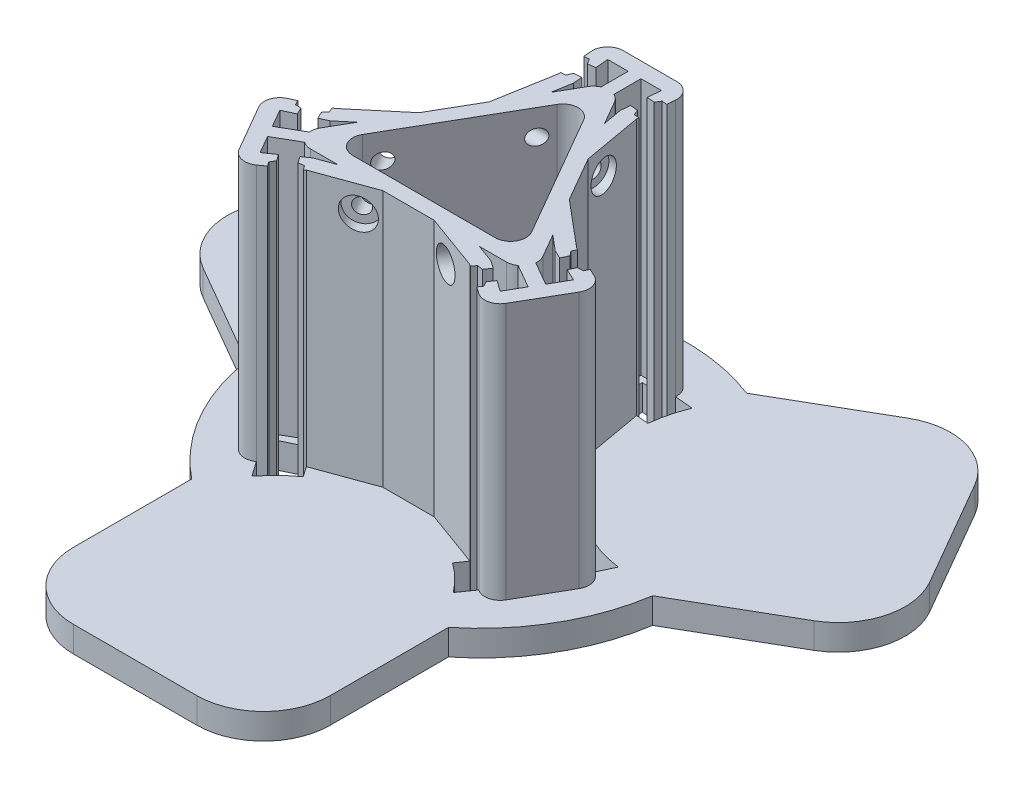
SolidWorks part; units mm, degrees
ref_plane "前视基准面" through (0, 0, 0) normal (0, 0, 1) x (1, 0, 0)
ref_plane "上视基准面" through (0, 0, 0) normal (0, 1, 0) x (1, 0, 0)
ref_plane "右视基准面" through (0, 0, 0) normal (1, 0, 0) x (0, 0, -1)
other "Configuration Table"
sketch "草图1" plane through (0, 0, 0) normal (0, 1, 0) x (1, 0, 0)
  line L0 (0, 0) -> (0, 132.3895) construction
  line L1 (0, 0) -> (0, -137.3851) construction
  line L2 (0, 0) -> (215.1509, 0) construction
  line L3 (0, 0) -> (134.3926, 77.5916) construction
  line L4 (0, 0) -> (-134.3926, 77.5916) construction
  line L5 (0, -40) -> (55.6916, -40) construction
  line L6 (-25, -31.225) -> (-25, -67.225)
  line L7 (-14.5416, 37.2631) -> (-45.7185, 55.2631)
  line L8 (25, -67.225) -> (-25, -67.225)
  line L9 (-70.7185, 11.9619) -> (-45.7185, 55.2631)
  line L10 (25, -31.225) -> (25, -67.225)
  line L11 (-39.5416, -6.0381) -> (-70.7185, 11.9619)
  line L12 (39.5416, -6.0381) -> (70.7185, 11.9619)
  line L13 (45.7185, 55.2631) -> (70.7185, 11.9619)
  line L14 (14.5416, 37.2631) -> (45.7185, 55.2631)
  circle A0 centre (0, 0) radius 40
  circle A1 centre (0, -40) radius 25 construction
  circle A2 centre (-34.641, 20) radius 25 construction
  circle A3 centre (34.641, 20) radius 25 construction
  point P16 (0, 0)
  point P23 (0, -67.225)
  point P32 (0, 0)
  dimension "D2" = 80
  dimension "D3" = 50
  dimension "D5" = 25
  dimension "D1" = 120
  dimension "D6" = 36
  dimension "D4" = 3
  dimension "D7" = 3
extrude "凸台-拉伸1" add sketch "草图1" along normal blind 5 contours A0 | A0 L7 L9 L11 | A0 L12 L13 L14 | A0 L6 L8 L10 region at (0, 0, 52.1112) region at (0, 0, 0) region at (-45.1296, 0, -26.0556) region at (45.1296, 0, -26.0556)
sketch "草图3" plane through (0, 5, 0) normal (0, 1, 0) x (1, 0, 0)
  line L0 (0, 28) -> (24.2487, -14)
  line L1 (0, 0) -> (134.3926, 77.5916) construction
  line L2 (0, 0) -> (0, 132.3895) construction
  line L3 (0, 0) -> (0, -137.3851) construction
  line L4 (0, 0) -> (-134.3926, 77.5916) construction
  line L5 (0, 0) -> (0, -137.3851) construction
  line L6 (0, 0) -> (-134.3926, 77.5916) construction
  line L7 (0, 0) -> (134.3926, 77.5916) construction
  line L8 (24.2487, -14) -> (-24.2487, -14)
  line L9 (-24.2487, -14) -> (0, 28)
  line L10 (0, 22) -> (19.0526, -11)
  line L11 (19.0526, -11) -> (-19.0526, -11)
  line L12 (-19.0526, -11) -> (0, 22)
  line L13 (5, -14) -> (15.9238, -17.9759)
  line L14 (15.9238, -17.9759) -> (24.3288, -23.8612)
  line L15 (0, 0) -> (24.2487, -14) construction
  line L17 (23.5295, -4.8024) -> (32.8288, -9.1388)
  line L18 (24.3288, -23.8612) -> (32.8288, -9.1388)
  line L19 (14.6244, 2.6699) -> (23.5295, -4.8024)
  line L20 (-5, -14) -> (-15.9238, -17.9759)
  line L21 (-15.9238, -17.9759) -> (-24.3288, -23.8612)
  line L22 (-32.8288, -9.1388) -> (-24.3288, -23.8612)
  line L23 (-23.5295, -4.8024) -> (-32.8288, -9.1388)
  line L24 (-14.6244, 2.6699) -> (-23.5295, -4.8024)
  line L25 (-9.6244, 11.3301) -> (-7.6057, 22.7784)
  line L26 (-7.6057, 22.7784) -> (-8.5, 33)
  line L27 (8.5, 33) -> (-8.5, 33)
  line L28 (7.6057, 22.7784) -> (8.5, 33)
  line L29 (9.6244, 11.3301) -> (7.6057, 22.7784)
  line L30 (-14.6244, 2.6699) -> (-23.5295, -4.8024)
  line L31 (-23.5295, -4.8024) -> (-32.8288, -9.1388)
  line L32 (-32.8288, -9.1388) -> (-24.3288, -23.8612)
  line L33 (-15.9238, -17.9759) -> (-24.3288, -23.8612)
  line L34 (-5, -14) -> (-15.9238, -17.9759)
  line L35 (5, -14) -> (15.9238, -17.9759)
  line L36 (15.9238, -17.9759) -> (24.3288, -23.8612)
  line L37 (24.3288, -23.8612) -> (32.8288, -9.1388)
  line L38 (23.5295, -4.8024) -> (32.8288, -9.1388)
  line L39 (14.6244, 2.6699) -> (23.5295, -4.8024)
  line L40 (5.529, -11) -> (17.321, -15.2919)
  line L41 (17.321, -15.2919) -> (23.3677, -19.5259)
  line L42 (23.3677, -19.5259) -> (28.5938, -10.4741)
  line L43 (21.9037, -7.3544) -> (28.5938, -10.4741)
  line L44 (12.2908, 0.7118) -> (21.9037, -7.3544)
  line L45 (-12.2908, 0.7118) -> (-21.9037, -7.3544)
  line L46 (-21.9037, -7.3544) -> (-28.5938, -10.4741)
  line L47 (-28.5938, -10.4741) -> (-23.3677, -19.5259)
  line L48 (-17.321, -15.2919) -> (-23.3677, -19.5259)
  line L49 (-5.529, -11) -> (-17.321, -15.2919)
  line L50 (6.7618, 10.2882) -> (4.5827, 22.6464)
  line L51 (4.5827, 22.6464) -> (5.2261, 30)
  line L52 (5.2261, 30) -> (-5.2261, 30)
  line L53 (-4.5827, 22.6464) -> (-5.2261, 30)
  line L54 (-6.7618, 10.2882) -> (-4.5827, 22.6464)
  line L55 (-12.696, 0.3717) -> (-21.9037, -7.3544) construction
  line L56 (-6.0261, -11.1809) -> (-17.321, -15.2919) construction
  line L57 (6.0261, -11.1809) -> (17.321, -15.2919) construction
  line L58 (12.696, 0.3717) -> (21.9037, -7.3544) construction
  line L59 (-6.6699, 10.8092) -> (-4.5827, 22.6464) construction
  line L60 (6.6699, 10.8092) -> (4.5827, 22.6464) construction
  point P13 (12.1244, 7)
  point P17 (0, 0)
  point P20 (28.5788, -16.5)
  point P38 (0, 0)
  dimension "D1" = 3
  dimension "D2" = 14
  dimension "D5" = 5
  dimension "D6" = 20
  dimension "D7" = 195
  dimension "D8" = 8.5
  dimension "D9" = 5
  dimension "D3" = 3
  dimension "D11" = 0
  dimension "D12" = 3
  dimension "D10" = 3
extrude "凸台-拉伸2" add sketch "草图3" along normal blind 50 contours L11 L49 L8 L40 | L0 L44 L43 L42 L41 L40 L8 L13 L14 L18 L17 L19 | L8 L49 L48 L47 L46 L45 L9 L24 L23 L22 L21 L20 | L12 L54 L9 L45 | L9 L54 L53 L52 L51 L50 L0 L29 L28 L27 L26 L25 | L50 L10 L44 L0 | L44 L10 L11 L40 L8 L0 | L49 L11 L12 L45 L9 L8 | L54 L12 L10 L50 L0 L9 region at (11.0102, 5, -6.3568) region at (7.6825, 5, -15.2732) region at (18.8298, 5, 1.3608) region at (5.7808, 5, -14.5686) region at (21.4232, 5, 9.5822) region at (-11.0102, 5, -6.3568) region at (0, 5, 12.7135) region at (-17.1502, 5, 0.936) region at (-15.8779, 5, 5.0251)
fillet "圆角1" radius 13 6 edges at (25, 2.5, 67.225) (-25, 2.5, 67.225) (-70.7185, 2.5, -11.9619) (-45.7185, 2.5, -55.2631) (70.7185, 2.5, -11.9619) (45.7185, 2.5, -55.2631)
fillet "圆角2" radius 3 6 edges at (0, 30, -28) (0, 30, -22) (24.2487, 30, 14) (19.0526, 30, 11) (-19.0526, 30, 11) (-24.2487, 30, 14)
sketch "草图6" plane through (0, 0, 0) normal (0, -1, 0) x (1, 0, 0)
  line L0 (0, 0) -> (0, 137.3851) construction
  line L1 (0, 0) -> (215.1509, 0) construction
  line L2 (0, 0) -> (0, -132.3895) construction
  line L3 (0, 0) -> (0, -132.3895) construction
  line L4 (0, 0) -> (215.1509, 0) construction
  circle A1 centre (0, 0) radius 3.5
  circle A2 centre (0, 7) radius 1.5
  circle A3 centre (7, 0) radius 1.5
  circle A4 centre (-7, 0) radius 1.5
  circle A5 centre (0, -7) radius 1.5
  dimension "D1" = 7
  dimension "D2" = 3
  dimension "D3" = 3
  dimension "D4" = 7
  dimension "D5" = 7
extrude "切除-拉伸1" cut sketch "草图6" against normal blind 5
fillet "圆角3" radius 3 6 edges at (-8.5, 30, -33) (8.5, 30, -33) (32.8288, 30, 9.1388) (-32.8288, 30, 9.1388) (-24.3288, 30, 23.8612) (24.3288, 30, 23.8612)
sketch "草图7" plane through (0, 0, 0) normal (1, 0, 0) x (0, 0, -1)
  line L0 (0, 0) -> (80.2302, 0) construction
  line L1 (0, 0) -> (132.3895, 0) construction
  line L2 (0, 0) -> (0, 66.7325) construction
  line L3 (15, 0) -> (15, 66.7325) construction
  line L5 (11.3301, 55) -> (22.7784, 55) construction
  circle A0 centre (15, 50) radius 1.5
  dimension "D2" = 3
  dimension "D3" = 5
  dimension "D1" = 15
extrude "切除-拉伸2" cut sketch "草图7" against normal blind 10 and the other way blind 10
ref_plane "基准面1" through (7, 0, 0) normal (1, 0, 0) x (0, 0, -1)
sketch "草图9" plane through (7, 0, 0) normal (1, 0, 0) x (0, 0, -1)
  circle A0 centre (15, 50) radius 3
  dimension "D1" = 6
extrude "切除-拉伸3" cut sketch "草图9" along normal blind 10
mirror "镜向1" about plane through (0, 0, 0) normal (1, 0, 0) of "切除-拉伸3"
ref_axis "基准轴1" through (0, 56.7, 0) along (0, -1, 0)
pattern_circular "阵列(圆周)1" count 3 over 360 about axis through (0, 56.7, 0) along (0, -1, 0) of "切除-拉伸2", "切除-拉伸3", "镜向1"
sketch "草图10" plane through (0, 5, 0) normal (0, 1, 0) x (1, 0, 0)
  line L2 (23.3677, -19.5259) -> (28.5938, -10.4741) construction
  line L3 (23.3677, -19.5259) -> (20.0911, -17.2316)
  line L4 (17.321, -15.2919) -> (23.3677, -19.5259) construction
  line L5 (23.3677, -19.5259) -> (28.5938, -10.4741)
  line L6 (0, 0) -> (25.9808, -15) construction
  line L7 (28.5938, -10.4741) -> (24.9686, -8.7836)
  line L8 (24.9686, -8.7836) -> (20.0911, -17.2316)
  line L9 (-23.3677, -19.5259) -> (-20.0911, -17.2316)
  line L10 (-20.0911, -17.2316) -> (-24.9686, -8.7836)
  line L11 (-28.5938, -10.4741) -> (-24.9686, -8.7836)
  line L12 (-28.5938, -10.4741) -> (-23.3677, -19.5259)
  line L13 (-5.2261, 30) -> (-4.8775, 26.0152)
  line L14 (-4.8775, 26.0152) -> (4.8775, 26.0152)
  line L15 (5.2261, 30) -> (4.8775, 26.0152)
  line L16 (5.2261, 30) -> (-5.2261, 30)
  line L17 (16.4545, -6.5) -> (14.1451, -2.5)
  line L18 (2.5981, 17.5) -> (16.4545, -6.5) construction
  line L19 (14.1451, -2.5) -> (9.2376, -11)
  line L20 (11.6913, -6.75) -> (15.1554, -8.75)
  line L21 (13.8564, -11) -> (16.4545, -6.5)
  line L22 (13.8564, -11) -> (9.2376, -11)
  line L23 (-16.4545, -6.5) -> (-13.8564, -11)
  line L24 (-13.8564, -11) -> (-9.2376, -11)
  line L25 (-9.2376, -11) -> (-14.1451, -2.5)
  line L26 (-11.6913, -6.75) -> (-15.1554, -8.75)
  line L27 (2.5981, 17.5) -> (-2.5981, 17.5)
  line L28 (-2.5981, 17.5) -> (-4.9075, 13.5)
  line L29 (-4.9075, 13.5) -> (4.9075, 13.5)
  line L30 (0, 13.5) -> (0, 17.5)
  line L31 (9.2376, -11) -> (13.8564, -11)
  line L32 (-16.4545, -6.5) -> (-14.1451, -2.5)
  line L33 (2.5981, 17.5) -> (4.9075, 13.5)
  arc A0 (2.5981, 17.5) -> (-2.5981, 17.5) centre (0, 16) ccw construction
  arc A1 (-16.4545, -6.5) -> (-13.8564, -11) centre (-13.8564, -8) ccw construction
  arc A2 (13.8564, -11) -> (16.4545, -6.5) centre (13.8564, -8) ccw construction
  arc A3 (2.5981, 17.5) -> (-2.5981, 17.5) centre (0, 16) ccw
  arc A4 (-16.4545, -6.5) -> (-13.8564, -11) centre (-13.8564, -8) ccw
  arc A5 (13.8564, -11) -> (16.4545, -6.5) centre (13.8564, -8) ccw
  point P22 (0, 0)
  point P41 (0, 0)
  line M19 (16.4545, -6.5) -> (2.5981, 17.5)
  arc M20 (2.5981, 17.5) -> (-2.5981, 17.5) centre (0, 16) ccw
  line M21 (-2.5981, 17.5) -> (-16.4545, -6.5)
  arc M22 (-16.4545, -6.5) -> (-13.8564, -11) centre (-13.8564, -8) ccw
  line M23 (-13.8564, -11) -> (13.8564, -11)
  arc M24 (13.8564, -11) -> (16.4545, -6.5) centre (13.8564, -8) ccw
  dimension "D1" = 4
  dimension "D3" = 4
  dimension "D4" = 3
  dimension "D2" = 3
extrude "切除-拉伸4" cut sketch "草图10" against normal blind 10 contours L30 L29 L27 M19 | L29 L30 L27 M21 | L20 L21 L19 M19 | L21 L20 L19 M23 | L26 L25 L23 M21 | L25 L26 L23 M23 | L23 M22 | L21 L6 A5 | L6 L21 M24 | L27 M20 region at (15.1793, 5, 9.9388) region at (16.1969, 5, 8.1763) region at (12.2779, 5, 9.3237) region at (14.2135, 5, 5.9712) region at (-12.2779, 5, 9.3237) region at (1.9356, 5, -15.2949) region at (-15.6881, 5, 9.0575) region at (-14.2135, 5, 5.9712) region at (-1.9356, 5, -15.2949) region at (0, 5, -18.1151)
chamfer "倒角1" distance 2 angle 45 3 edges at (0, 5, 11) (9.5263, 5, -5.5) (-9.5263, 5, -5.5)
sketch "草图12" plane through (0, 55, 0) normal (0, 1, 0) x (1, 0, 0)
  line L0 (0, 0) -> (0, 78.5225) construction
  line L2 (1.25, 0) -> (1.25, 78.5225) construction
  line L3 (-1.25, 0) -> (-1.25, 78.5225) construction
  line L4 (-1.25, 30) -> (1.25, 30)
  line L5 (5.2261, 30) -> (-5.2261, 30) construction
  line L6 (1.25, 30) -> (1.25, 24.7272)
  line L7 (-1.25, 30) -> (-1.25, 24.7272)
  line L8 (25.3558, -16.0825) -> (20.7894, -13.4461)
  line L9 (26.6058, -13.9175) -> (22.0394, -11.2811)
  line L10 (26.6058, -13.9175) -> (25.3558, -16.0825)
  line L11 (-26.6058, -13.9175) -> (-22.0394, -11.2811)
  line L12 (-25.3558, -16.0825) -> (-20.7894, -13.4461)
  line L13 (-25.3558, -16.0825) -> (-26.6058, -13.9175)
  arc A0 (2.5981, 23.5) -> (-2.5981, 23.5) centre (0, 22) ccw construction
  arc A1 (2.5981, 23.5) -> (-2.5981, 23.5) centre (0, 22) ccw construction
  arc A2 (1.25, 24.7272) -> (-1.25, 24.7272) centre (0, 22) ccw
  arc A3 (20.7894, -13.4461) -> (22.0394, -11.2811) centre (19.0526, -11) ccw
  arc A4 (-22.0394, -11.2811) -> (-20.7894, -13.4461) centre (-19.0526, -11) ccw
  point P31 (0, 0)
  dimension "D1" = 1.25
  dimension "D2" = 1.25
  dimension "D3" = 3
extrude "凸台-拉伸3" add sketch "草图12" against normal up to surface (50 mm away) up to face at (-20.7462, 5, 11.9778)
sketch "草图14" plane through (0, 55, 0) normal (0, 1, 0) x (1, 0, 0)
  line L0 (0, 0) -> (28.5788, -16.5) construction
  line L1 (25.9658, -21.0259) -> (31.1919, -11.9741) construction
  line L5 (0, -15) -> (39.0911, -15) construction
  line L6 (0, 0) -> (0, -137.3851) construction
  line L7 (0, -40) -> (0, -15) construction
  line L8 (0, -40) -> (25.96, -11.1685) construction
  line L10 (15.9238, -17.9759) -> (21.647, -21.9834) construction
  line L15 (18.3199, -19.6537) -> (23.51, -12.2415) construction
  line L16 (15.9238, -17.9759) -> (21.647, -21.9834) construction
  line L29 (17.321, -15.2919) -> (23.3677, -19.5259) construction
  line L35 (16.272, -18.2198) -> (20.3678, -21.0876)
  line L36 (20.3678, -21.0876) -> (20.9413, -20.2685)
  line L37 (20.9413, -20.2685) -> (20.409, -19.2853)
  line L38 (20.409, -19.2853) -> (21.2693, -18.0566)
  line L39 (21.2693, -18.0566) -> (18.8119, -16.3359)
  line L40 (16.272, -18.2198) -> (16.8456, -17.4006)
  line L41 (16.8456, -17.4006) -> (17.9515, -17.5646)
  line L42 (17.9515, -17.5646) -> (18.8119, -16.3359)
  line L43 (23.9148, -4.9821) -> (23.4922, -5.8884)
  line L44 (23.4922, -5.8884) -> (24.1872, -6.7642)
  line L45 (24.1872, -6.7642) -> (23.5532, -8.1236)
  line L46 (26.2722, -9.3915) -> (23.5532, -8.1236)
  line L47 (26.9061, -8.032) -> (26.2722, -9.3915)
  line L48 (28.0237, -8.0015) -> (26.9061, -8.032)
  line L49 (28.4463, -7.0952) -> (28.0237, -8.0015)
  line L50 (23.9148, -4.9821) -> (28.4463, -7.0952)
  line L51 (-23.9148, -4.9821) -> (-28.4463, -7.0952)
  line L52 (-28.4463, -7.0952) -> (-28.0237, -8.0015)
  line L53 (-28.0237, -8.0015) -> (-26.9061, -8.032)
  line L54 (-26.9061, -8.032) -> (-26.2722, -9.3915)
  line L55 (-26.2722, -9.3915) -> (-23.5532, -8.1236)
  line L56 (-24.1872, -6.7642) -> (-23.5532, -8.1236)
  line L57 (-23.4922, -5.8884) -> (-24.1872, -6.7642)
  line L58 (-23.9148, -4.9821) -> (-23.4922, -5.8884)
  line L59 (-16.272, -18.2198) -> (-16.8456, -17.4006)
  line L60 (-16.8456, -17.4006) -> (-17.9515, -17.5646)
  line L61 (-17.9515, -17.5646) -> (-18.8119, -16.3359)
  line L62 (-21.2693, -18.0566) -> (-18.8119, -16.3359)
  line L63 (-20.409, -19.2853) -> (-21.2693, -18.0566)
  line L64 (-20.9413, -20.2685) -> (-20.409, -19.2853)
  line L65 (-20.3678, -21.0876) -> (-20.9413, -20.2685)
  line L66 (-16.272, -18.2198) -> (-20.3678, -21.0876)
  line L67 (7.6428, 23.2019) -> (8.0786, 28.1828)
  line L68 (8.0786, 28.1828) -> (7.0824, 28.27)
  line L69 (7.0824, 28.27) -> (6.4971, 27.3174)
  line L70 (6.4971, 27.3174) -> (5.0028, 27.4481)
  line L71 (5.0028, 27.4481) -> (4.7413, 24.4595)
  line L72 (6.2356, 24.3288) -> (4.7413, 24.4595)
  line L73 (6.6466, 23.289) -> (6.2356, 24.3288)
  line L74 (7.6428, 23.2019) -> (6.6466, 23.289)
  line L75 (-7.6428, 23.2019) -> (-6.6466, 23.289)
  line L76 (-6.6466, 23.289) -> (-6.2356, 24.3288)
  line L77 (-6.2356, 24.3288) -> (-4.7413, 24.4595)
  line L78 (-5.0028, 27.4481) -> (-4.7413, 24.4595)
  line L79 (-6.4971, 27.3174) -> (-5.0028, 27.4481)
  line L80 (-7.0824, 28.27) -> (-6.4971, 27.3174)
  line L81 (-8.0786, 28.1828) -> (-7.0824, 28.27)
  line L82 (-7.6428, 23.2019) -> (-8.0786, 28.1828)
  circle A0 centre (0, -40) radius 25 construction
  point P29 (20.0406, -17.1962)
  point P32 (20.0406, -17.1962)
  point P74 (0, 0)
  dimension "D1" = 42
  dimension "D2" = 2.5
  dimension "D3" = 1
  dimension "D4" = 1.5
  dimension "D5" = 1.5
  dimension "D6" = 3
extrude "切除-拉伸5" cut sketch "草图14" against normal up to surface (50 mm away) up to face at (0, 5, 0)
sketch "草图15" plane through (0, 5, 0) normal (0, 1, 0) x (1, 0, 0)
  line L0 (29.8617, -7.7552) -> (31.2539, -4.7695) construction
  line L1 (28.4463, -7.0952) -> (29.8617, -7.7552) construction
  line L2 (28.0237, -8.0015) -> (28.4463, -7.0952) construction
  line L3 (26.9061, -8.032) -> (28.0237, -8.0015) construction
  line L4 (26.2722, -9.3915) -> (26.9061, -8.032) construction
  line L5 (26.2722, -9.3915) -> (27.1785, -9.8141) construction
  line L6 (23.5532, -8.1236) -> (22.6469, -7.701) construction
  line L7 (24.1872, -6.7642) -> (23.5532, -8.1236) construction
  line L8 (23.4922, -5.8884) -> (24.1872, -6.7642) construction
  line L9 (23.9148, -4.9821) -> (23.4922, -5.8884) construction
  line L10 (23.5295, -4.8024) -> (23.9148, -4.9821) construction
  line L11 (23.5295, -4.8024) -> (24.4499, -2.8285) construction
  line L12 (29.7407, -7.4229) -> (30.9952, -4.7327) construction
  line L13 (28.3254, -6.763) -> (29.7407, -7.4229) construction
  line L14 (27.8624, -7.7558) -> (28.3254, -6.763) construction
  line L15 (4.8409, 28.4661) -> (2.8485, 28.6404)
  line L16 (4.732, 27.2208) -> (4.8409, 28.4661)
  line L17 (6.6292, 27.0549) -> (4.732, 27.2208)
  line L18 (7.2145, 28.0075) -> (6.6292, 27.0549)
  line L19 (8.3058, 27.912) -> (7.2145, 28.0075)
  line L20 (8.4419, 29.4677) -> (8.3058, 27.912)
  line L21 (11.3989, 29.209) -> (8.4419, 29.4677)
  line L22 (7.8766, 23.0056) -> (9.8025, 22.8371)
  line L23 (7.9136, 23.4291) -> (7.8766, 23.0056)
  line L24 (6.8223, 23.5246) -> (7.9136, 23.4291)
  line L25 (6.4113, 24.5644) -> (6.8223, 23.5246)
  line L26 (4.5141, 24.7304) -> (6.4113, 24.5644)
  line L27 (4.4051, 23.4851) -> (4.5141, 24.7304)
  line L28 (3.2097, 23.5897) -> (4.4051, 23.4851)
  line L29 (2.8485, 28.6404) -> (3.2097, 23.5897)
  line L30 (4.8409, 28.4661) -> (2.8485, 28.6404)
  line L31 (4.732, 27.2208) -> (4.8409, 28.4661)
  line L32 (6.6292, 27.0549) -> (4.732, 27.2208)
  line L33 (7.2145, 28.0075) -> (6.6292, 27.0549)
  line L34 (8.3058, 27.912) -> (7.2145, 28.0075)
  line L35 (8.4419, 29.4677) -> (8.3058, 27.912)
  line L36 (11.3989, 29.209) -> (8.4419, 29.4677)
  line L37 (7.8766, 23.0056) -> (9.8025, 22.8371)
  line L38 (7.9136, 23.4291) -> (7.8766, 23.0056)
  line L39 (6.8223, 23.5246) -> (7.9136, 23.4291)
  line L40 (6.4113, 24.5644) -> (6.8223, 23.5246)
  line L41 (4.5141, 24.7304) -> (6.4113, 24.5644)
  line L42 (4.4051, 23.4851) -> (4.5141, 24.7304)
  line L43 (3.2097, 23.5897) -> (4.4051, 23.4851)
  line L44 (2.8485, 28.6404) -> (3.2097, 23.5897)
  line L45 (26.7448, -7.7863) -> (27.8624, -7.7558) construction
  line L46 (25.9399, -9.5124) -> (26.7448, -7.7863) construction
  line L47 (25.9399, -9.5124) -> (27.0728, -10.0407) construction
  line L48 (27.0728, -10.0407) -> (26.2276, -11.8533) construction
  line L49 (22.0341, -9.0152) -> (26.2276, -11.8533) construction
  line L50 (22.5413, -7.9276) -> (22.0341, -9.0152) construction
  line L51 (23.6742, -8.4559) -> (22.5413, -7.9276) construction
  line L52 (24.479, -6.7298) -> (23.6742, -8.4559) construction
  line L53 (23.784, -5.854) -> (24.479, -6.7298) construction
  line L54 (24.247, -4.8612) -> (23.784, -5.854) construction
  line L55 (23.8617, -4.6815) -> (24.247, -4.8612) construction
  line L56 (23.8617, -4.6815) -> (24.6788, -2.9293) construction
  line L57 (8.2147, 29.7385) -> (11.4965, 29.4514) construction
  line L58 (8.0786, 28.1828) -> (8.2147, 29.7385) construction
  line L59 (7.0824, 28.27) -> (8.0786, 28.1828) construction
  line L60 (6.4971, 27.3174) -> (7.0824, 28.27) construction
  line L61 (5.0028, 27.4481) -> (6.4971, 27.3174) construction
  line L62 (5.0028, 27.4481) -> (5.09, 28.4443) construction
  line L63 (4.7413, 24.4595) -> (4.6542, 23.4633) construction
  line L64 (6.2356, 24.3288) -> (4.7413, 24.4595) construction
  line L65 (6.6466, 23.289) -> (6.2356, 24.3288) construction
  line L66 (7.6428, 23.2019) -> (6.6466, 23.289) construction
  line L67 (7.6057, 22.7784) -> (7.6428, 23.2019) construction
  line L68 (29.8617, -7.7552) -> (31.2539, -4.7695)
  line L69 (28.4463, -7.0952) -> (29.8617, -7.7552)
  line L70 (28.0237, -8.0015) -> (28.4463, -7.0952)
  line L71 (26.9061, -8.032) -> (28.0237, -8.0015)
  line L72 (26.2722, -9.3915) -> (26.9061, -8.032)
  line L73 (26.2722, -9.3915) -> (27.1785, -9.8141)
  line L74 (23.5532, -8.1236) -> (22.6469, -7.701)
  line L75 (24.1872, -6.7642) -> (23.5532, -8.1236)
  line L76 (23.4922, -5.8884) -> (24.1872, -6.7642)
  line L77 (23.9148, -4.9821) -> (23.4922, -5.8884)
  line L78 (23.5295, -4.8024) -> (23.9148, -4.9821)
  line L79 (23.5295, -4.8024) -> (24.4499, -2.8285)
  line L80 (29.7407, -7.4229) -> (30.9952, -4.7327)
  line L81 (28.3254, -6.763) -> (29.7407, -7.4229)
  line L82 (27.8624, -7.7558) -> (28.3254, -6.763)
  line L83 (26.7448, -7.7863) -> (27.8624, -7.7558)
  line L84 (25.9399, -9.5124) -> (26.7448, -7.7863)
  line L85 (25.9399, -9.5124) -> (27.0728, -10.0407)
  line L86 (27.0728, -10.0407) -> (26.2276, -11.8533)
  line L87 (22.0341, -9.0152) -> (26.2276, -11.8533)
  line L88 (22.5413, -7.9276) -> (22.0341, -9.0152)
  line L89 (23.6742, -8.4559) -> (22.5413, -7.9276)
  line L90 (24.479, -6.7298) -> (23.6742, -8.4559)
  line L91 (23.784, -5.854) -> (24.479, -6.7298)
  line L92 (24.247, -4.8612) -> (23.784, -5.854)
  line L93 (23.8617, -4.6815) -> (24.247, -4.8612)
  line L94 (23.8617, -4.6815) -> (24.6788, -2.9293)
  line L95 (8.2147, 29.7385) -> (11.4965, 29.4514)
  line L96 (8.0786, 28.1828) -> (8.2147, 29.7385)
  line L97 (7.0824, 28.27) -> (8.0786, 28.1828)
  line L98 (6.4971, 27.3174) -> (7.0824, 28.27)
  line L99 (5.0028, 27.4481) -> (6.4971, 27.3174)
  line L100 (5.0028, 27.4481) -> (5.09, 28.4443)
  line L101 (4.7413, 24.4595) -> (4.6542, 23.4633)
  line L102 (6.2356, 24.3288) -> (4.7413, 24.4595)
  line L103 (6.6466, 23.289) -> (6.2356, 24.3288)
  line L104 (7.6428, 23.2019) -> (6.6466, 23.289)
  line L105 (7.6057, 22.7784) -> (7.6428, 23.2019)
  line L106 (22.4203, -7.5954) -> (21.7175, -9.1027)
  line L107 (21.7175, -9.1027) -> (26.3302, -12.2247)
  line L108 (27.405, -9.9198) -> (26.3302, -12.2247)
  line L109 (26.2722, -9.3915) -> (27.405, -9.9198)
  line L110 (26.2722, -9.3915) -> (26.9061, -8.032)
  line L111 (26.9061, -8.032) -> (28.0237, -8.0015)
  line L112 (28.0237, -8.0015) -> (28.4463, -7.0952)
  line L113 (28.4463, -7.0952) -> (29.8617, -7.7552)
  line L114 (29.8617, -7.7552) -> (31.3646, -4.5322)
  line L115 (23.5295, -4.8024) -> (24.5556, -2.6019)
  line L116 (23.5295, -4.8024) -> (23.9148, -4.9821)
  line L117 (23.9148, -4.9821) -> (23.4922, -5.8884)
  line L118 (23.4922, -5.8884) -> (24.1872, -6.7642)
  line L119 (24.1872, -6.7642) -> (23.5532, -8.1236)
  line L120 (23.5532, -8.1236) -> (22.4203, -7.5954)
  line L121 (5.1118, 28.6933) -> (2.5783, 28.915)
  line L122 (2.5783, 28.915) -> (2.9755, 23.3592)
  line L123 (2.9755, 23.3592) -> (4.6324, 23.2143)
  line L124 (4.6324, 23.2143) -> (4.7413, 24.4595)
  line L125 (4.7413, 24.4595) -> (6.2356, 24.3288)
  line L126 (6.2356, 24.3288) -> (6.6466, 23.289)
  line L127 (6.6466, 23.289) -> (7.6428, 23.2019)
  line L128 (7.6428, 23.2019) -> (7.6057, 22.7784)
  line L129 (7.6057, 22.7784) -> (10.0245, 22.5668)
  line L130 (11.7573, 29.4286) -> (8.2147, 29.7385)
  line L131 (8.2147, 29.7385) -> (8.0786, 28.1828)
  line L132 (8.0786, 28.1828) -> (7.0824, 28.27)
  line L133 (7.0824, 28.27) -> (6.4971, 27.3174)
  line L134 (6.4971, 27.3174) -> (5.0028, 27.4481)
  line L135 (5.0028, 27.4481) -> (5.1118, 28.6933)
  arc A0 (24.6788, -2.9293) -> (30.9952, -4.7327) centre (34.641, 20) ccw construction
  arc A1 (11.3989, 29.209) -> (9.8025, 22.8371) centre (34.641, 20) ccw
  arc A2 (11.3989, 29.209) -> (9.8025, 22.8371) centre (34.641, 20) ccw
  arc A3 (24.6788, -2.9293) -> (30.9952, -4.7327) centre (34.641, 20) ccw
  arc A4 (24.5556, -2.6019) -> (31.3646, -4.5322) centre (34.641, 20) ccw
  arc A5 (11.7573, 29.4286) -> (10.0245, 22.5668) centre (34.641, 20) ccw
  dimension "D1" = 0
  dimension "D2" = 0.25
extrude "切除-拉伸6" cut sketch "草图15" against normal blind 5 contours A2 L36 L35 L34 L33 L32 L31 L30 L44 L43 L42 L41 L40 L39 L38 L37 | A5 L130 L95 L96 L97 L98 L99 L100 L135 L121 L122 L123 L124 L101 L102 L103 L104 L105 L129 L36 A2 L37 L38 L39 L40 L41 L42 L43 L44 L30 L31 L32 L33 L34 L35 | A3 L94 L93 L92 L91 L90 L89 L88 L87 L86 L85 L84 L83 L82 L81 L80 | A4 L115 L79 L78 L77 L76 L75 L74 L120 L106 L107 L108 L109 L73 L72 L71 L70 L69 L68 L114 L94 A3 L80 L81 L82 L83 L84 L85 L86 L87 L88 L89 L90 L91 L92 L93 region at (7.1553, 5, -26.1562) region at (29.2116, 5, 7.3017) region at (26.2296, 5, 6.8814) region at (9.8454, 5, -29.4789)
pattern_circular "阵列(圆周)2" count 3 over 360 about axis through (0, 56.7, 0) along (0, -1, 0) of "切除-拉伸6"
